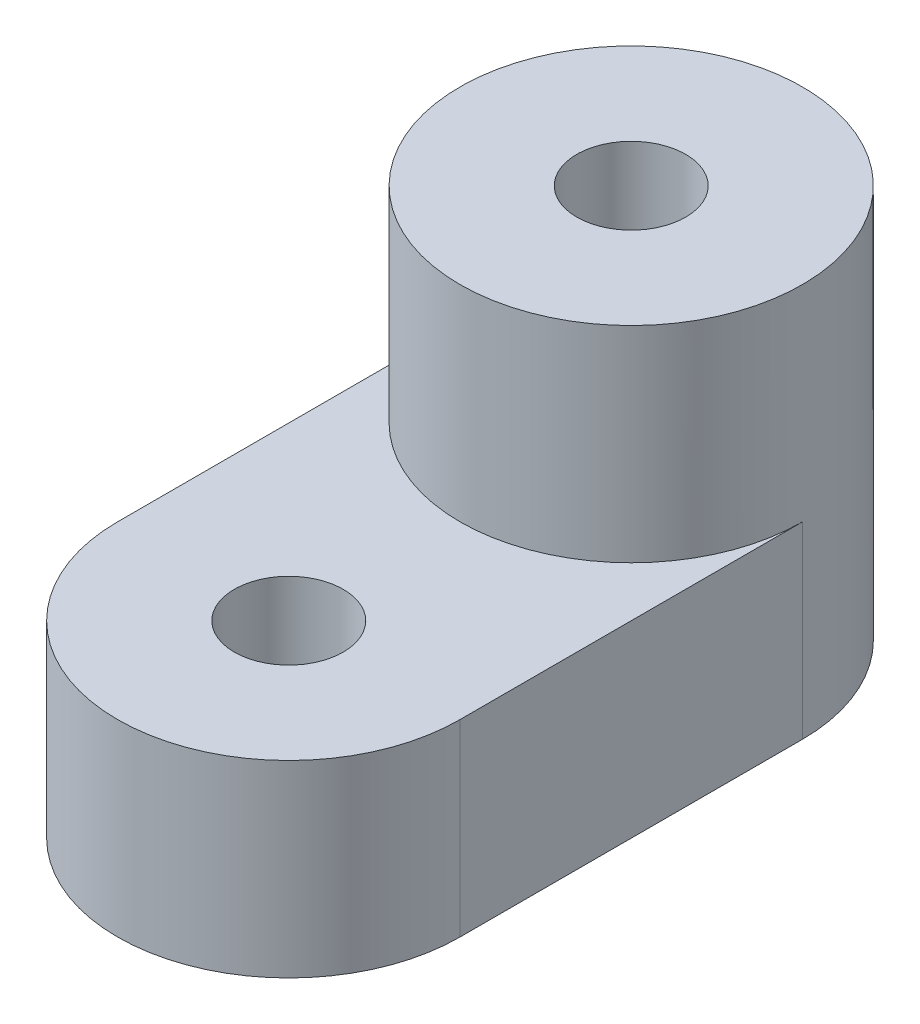
SolidWorks part; units mm, degrees
ref_plane "Front Plane" through (0, 0, 0) normal (0, 0, 1) x (1, 0, 0)
ref_plane "Top Plane" through (0, 0, 0) normal (0, 1, 0) x (1, 0, 0)
ref_plane "Right Plane" through (0, 0, 0) normal (1, 0, 0) x (0, 0, -1)
sketch "Sketch1" plane through (0, 0, 0) normal (0, 1, 0) x (1, 0, 0)
  line L2 (-5, 0) -> (-5, 10)
  line L3 (-5, 10) -> (5, 10)
  line L4 (5, 0) -> (5, 10)
  circle A0 centre (0, 0) radius 5
  point P0 (0, 0)
  dimension "D3" = 10
  dimension "D1" = 10
  dimension "D2" = 5
extrude "Boss-Extrude1" add sketch "Sketch1" along normal blind 5.5 contours A0 L4 L3 L2 | A0 region at (0, 0, -6.861)
sketch "Sketch2" plane through (0, 5.5, 0) normal (0, 1, 0) x (1, 0, 0)
  circle A0 centre (0, 0) radius 1.59
extrude "Cut-Extrude1" cut sketch "Sketch2" against normal through all
sketch "Sketch3" plane through (0, 5.5, 0) normal (0, 1, 0) x (1, 0, 0)
  line L0 (-5, 0) -> (-5, 10) construction
  circle A0 centre (0, 10) radius 5
  dimension "D2" = 10
  dimension "D1" = 10
  dimension "D3" = 5
extrude "Boss-Extrude2" add sketch "Sketch3" along normal blind 6 and the other way up to surface (5.5 mm away) other way up to face at (0, 0, 1.59)
sketch "Sketch4" plane through (0, 11.5, 0) normal (0, 1, 0) x (1, 0, 0)
  circle A0 centre (0, 10) radius 1.59
extrude "Cut-Extrude2" cut sketch "Sketch4" against normal blind 10
sketch "Sketch6" plane through (0, 5.5, 0) normal (0, 1, 0) x (1, 0, 0)
sketch "Sketch7" plane through (-5, 0, 0) normal (-1, 0, 0) x (0, 0, 1)
  line L0 (-10.1052, 5.5) -> (-10.1052, 0)
  line L1 (0, 5.5) -> (-10, 5.5) construction
  line L2 (0, 0) -> (-10, 0) construction
sketch "Sketch8" plane through (5, 0, 0) normal (1, 0, 0) x (0, 0, -1)
  line L0 (9.8459, 5.5) -> (9.8459, 0)
  line L1 (0, 5.5) -> (10, 5.5) construction
  line L2 (0, 0) -> (10, 0) construction
